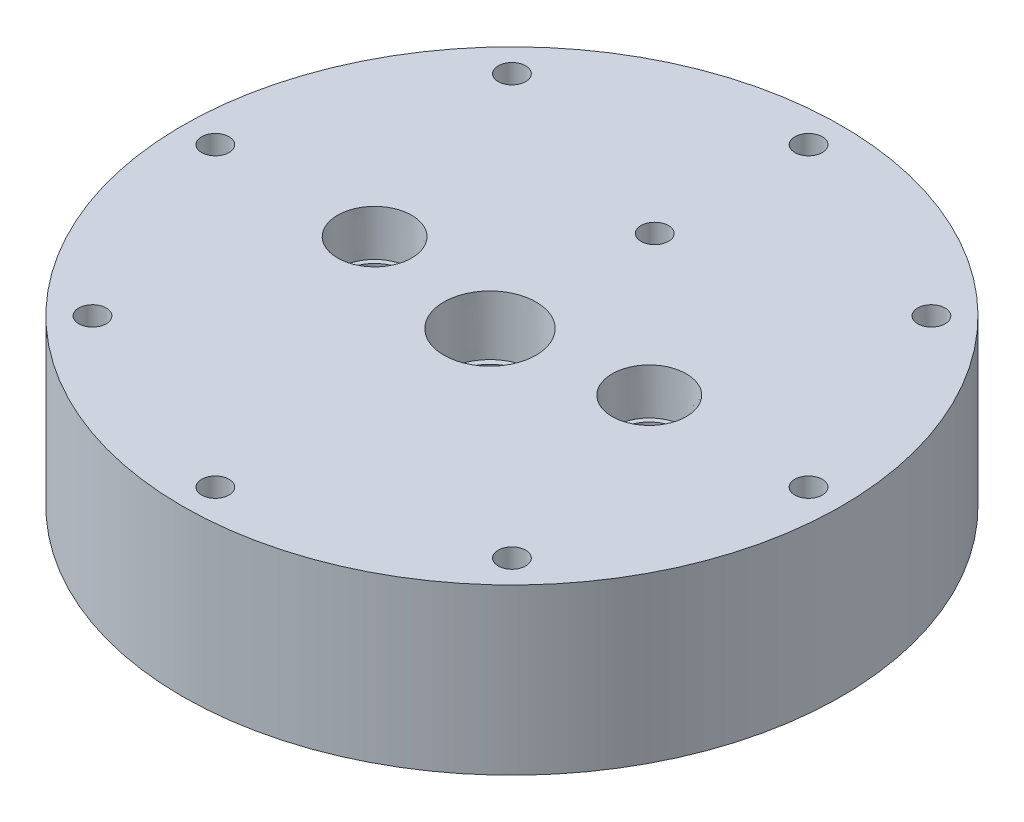
SolidWorks part; units mm, degrees
ref_plane "Front Plane" through (0, 0, 0) normal (0, 0, 1) x (1, 0, 0)
ref_plane "Top Plane" through (0, 0, 0) normal (0, 1, 0) x (1, 0, 0)
ref_plane "Right Plane" through (0, 0, 0) normal (1, 0, 0) x (0, 0, -1)
ref_axis "Axial" through (0, 53.34, 0) along (0, -1, 0)
ref_plane "Bottom Plane" through (0, -50.8, 0) normal (0, 1, 0) x (1, 0, 0)
sketch "Sketch1" plane through (0, 0, 0) normal (0, 1, 0) x (1, 0, 0)
  circle A0 centre (0, 0) radius 76.2
  dimension "D1" = 152.4
extrude "Billet" add sketch "Sketch1" against normal blind 50.8
sketch "Sketch3" plane through (0, -50.8, 0) normal (0, 1, 0) x (1, 0, 0)
  line L0 (0, 81.5114) -> (0, -83.2162) construction
  circle A0 centre (0, -5.08) radius 19.05
  point P6 (0, -12.6795)
  dimension "D1" = 38.1
  dimension "D2" = 5.08
extrude "Lox Plate" cut sketch "Sketch3" along normal blind 13.97
sketch "Sketch5" plane through (0, -50.8, 0) normal (0, 1, 0) x (1, 0, 0)
  line L0 (0, 57.2178) -> (0, -49.9723) construction
  circle A0 centre (0, -5.08) radius 13.97
  point P6 (0, -16.0892)
  dimension "D1" = 27.94
  dimension "D2" = 5.08
extrude "Lox Dome" cut sketch "Sketch5" along normal blind 20.32
sketch "Sketch7" plane through (0, 0, 0) normal (0, 1, 0) x (1, 0, 0)
  circle A1 centre (0, 0) radius 76.2
  dimension "D2" = 152.4
extrude "Top Mill" cut sketch "Sketch7" against normal blind 12.7
sketch "Sketch11" plane through (0, -50.8, 0) normal (0, 1, 0) x (1, 0, 0)
  line L0 (0, 82.3071) -> (0, -82.946) construction
  circle A0 centre (0, 68.58) radius 3.175
  dimension "D1" = 6.35
  dimension "D2" = 68.58
extrude "1/4\" Bolt Hole" cut sketch "Sketch11" along normal up to next
pattern_circular "Bolt Pattern" count 8 over 360 about axis through (0, 53.34, 0) along (0, -1, 0) of "1/4\" Bolt Hole"
sketch "Sketch12" plane through (0, -50.8, 0) normal (0, 1, 0) x (1, 0, 0)
  circle A0 centre (0, 0) radius 60.96
  dimension "D1" = 121.92
extrude "Kerosene Plate" cut sketch "Sketch12" along normal blind 10.16
hole_wizard "Lox Inlet-1/2 NPT Tapped Hole3" positions "Sketch20" profile "Sketch21" size "1/2" standard "ANSI Inch" end condition through all
sketch "Sketch20" plane through (0, -12.7, 0) normal (0, 1, 0) x (1, 0, 0)
  line L0 (0, 40.1697) -> (0, -38.6779) construction
  point P8 (0, -5.08)
  dimension "D1" = 5.08
sketch "Sketch21" plane through (0, -12.7, 5.08) normal (1, 0, 0) x (0, 0, 1)
  line L0 (0, 0) -> (0, 38.1)
  line L1 (0, 38.1) -> (8.9281, 38.1)
  line L2 (-10.2617, 13.462) -> (-10.6647, 0) construction
  line L3 (8.9281, 38.1) -> (8.9281, 13.462)
  line L4 (8.9281, 13.462) -> (10.2617, 13.462)
  line L5 (10.2617, 13.462) -> (10.6647, 0)
  line L7 (10.6647, 0) -> (0, 0)
  line L8 (0, -6.35) -> (0, 107.95) construction
  line L11 (-8.9281, 13.462) -> (-10.2617, 13.462) construction
  dimension "Thru Tap Drill Dia." = 17.8562
  dimension "Thru Tap Drill Depth" = 38.1
  dimension "Thread Dia." = 21.3295
  dimension "Thread Angle" = 3.43
  dimension "Thread Depth" = 13.462
sketch "Sketch26" plane through (0, -36.83, 0) normal (0, -1, 0) x (1, 0, 0)
  line L0 (0, 61.7216) -> (0, -111.1039) construction
  circle A0 centre (0, 5.08) radius 16.51
  circle A1 centre (0, 5.08) radius 17.78
  point P7 (0, 19.05)
  point P8 (0, 25.5091)
  point P9 (0, 0)
  dimension "D1" = 35.56
  dimension "D2" = 33.02
  dimension "D3" = 5.08
extrude "Lox Plate O Ring" cut sketch "Sketch26" against normal blind 1.27
hole_wizard "Kerosene Inlet-3/8 NPT Tapped Hole1" positions "Sketch24" profile "Sketch25" size "3/8" standard "ANSI Inch" end condition through all
sketch "Sketch24" plane through (0, -12.7, 0) normal (0, 1, 0) x (1, 0, 0)
  point P0 (-31.75, 0)
  point P2 (31.75, 0)
  dimension "D1" = 31.75
  dimension "D2" = 31.75
sketch "Sketch25" plane through (-31.75, -12.7, 0) normal (1, 0, 0) x (0, 0, 1)
  line L0 (0, 0) -> (0, 38.1)
  line L1 (0, 38.1) -> (7.1374, 38.1)
  line L2 (-8.2632, 10.414) -> (-8.575, 0) construction
  line L3 (7.1374, 38.1) -> (7.1374, 10.414)
  line L4 (7.1374, 10.414) -> (8.2632, 10.414)
  line L5 (8.2632, 10.414) -> (8.575, 0)
  line L7 (8.575, 0) -> (0, 0)
  line L8 (0, -6.35) -> (0, 107.95) construction
  line L11 (-7.1374, 10.414) -> (-8.2632, 10.414) construction
  dimension "Thru Tap Drill Dia." = 14.2748
  dimension "Thru Tap Drill Depth" = 38.1
  dimension "Thread Dia." = 17.15
  dimension "Thread Angle" = 3.43
  dimension "Thread Depth" = 10.414
sketch "Sketch14" plane through (0, 0, 0) normal (0, 1, 0) x (1, 0, 0)
  line L0 (0, 82.1507) -> (0, -86.6258) construction
  circle A0 centre (0, 33.02) radius 3.175
  dimension "D1" = 6.35
  dimension "D2" = 33.02
extrude "Manifold hole" cut sketch "Sketch14" against normal up to next
sketch "Sketch15" plane through (0, -40.64, 0) normal (0, 1, 0) x (1, 0, 0)
  line L0 (0, 72.5611) -> (0, -49.1199) construction
  circle A0 centre (0, 33.02) radius 7.62
  circle A1 centre (0, 33.02) radius 8.89
  dimension "D1" = 15.24
  dimension "D2" = 17.78
extrude "Manifold seal" cut sketch "Sketch15" along normal blind 1.27
